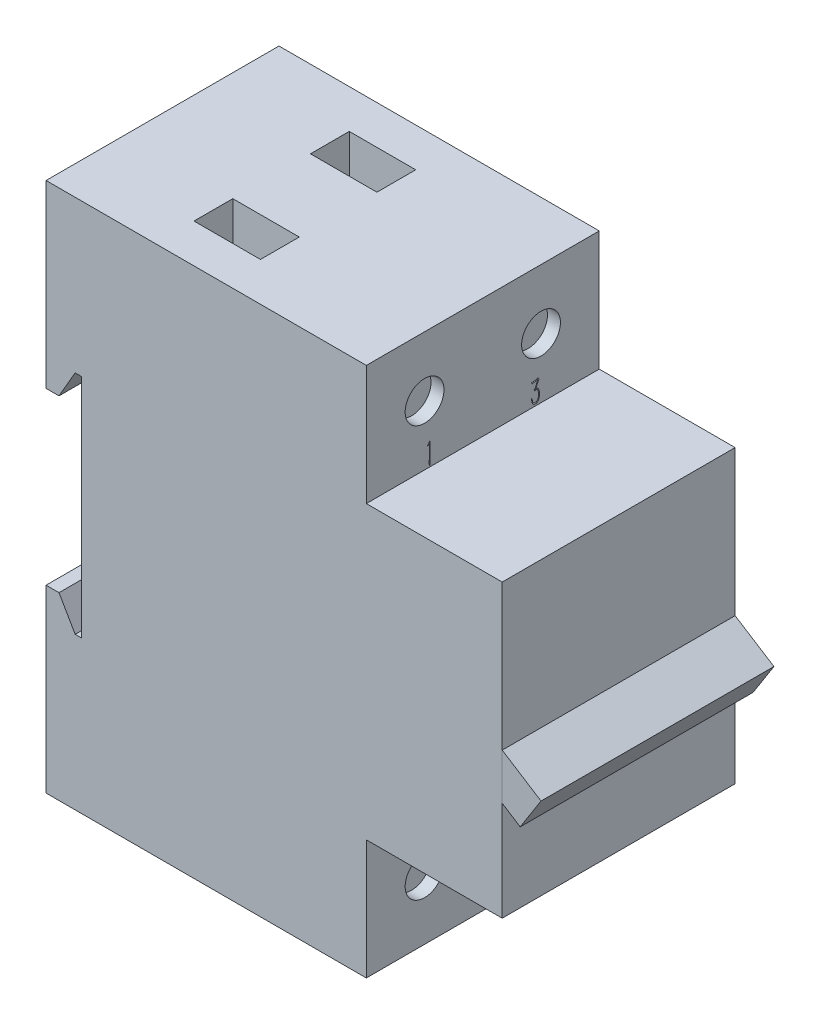
SolidWorks part; units mm, degrees
material "普通碳钢"
ref_plane "前视基准面" through (0, 0, 0) normal (0, 0, 1) x (1, 0, 0)
ref_plane "上视基准面" through (0, 0, 0) normal (0, 1, 0) x (1, 0, 0)
ref_plane "右视基准面" through (0, 0, 0) normal (1, 0, 0) x (0, 0, -1)
sketch "草图1" plane through (0, 0, 0) normal (0, 0, 1) x (1, 0, 0)
  line L0 (0, 0) -> (97.4474, 0) construction
  line L1 (0, 13.1699) -> (2, 13.1699)
  line L2 (2, 13.1699) -> (4.5, 17.5)
  line L3 (4.5, 17.5) -> (5.5, 17.5)
  line L4 (5.5, 17.5) -> (5.5, -17.5)
  line L5 (0, 13.1699) -> (0, 41)
  line L6 (0, 41) -> (49.5, 41)
  line L7 (49.5, 41) -> (49.5, 22.5)
  line L8 (49.5, 22.5) -> (70.5, 22.5)
  line L9 (70.5, 22.5) -> (70.5, -22.5)
  line L10 (49.5, -22.5) -> (70.5, -22.5)
  line L11 (49.5, -41) -> (49.5, -22.5)
  line L12 (0, -41) -> (49.5, -41)
  line L13 (0, -13.1699) -> (0, -41)
  line L14 (4.5, -17.5) -> (5.5, -17.5)
  line L15 (2, -13.1699) -> (4.5, -17.5)
  line L16 (0, -13.1699) -> (2, -13.1699)
  point P14 (70.5, 0)
  point P19 (5.5, 0)
  dimension "D1" = 35
  dimension "D2" = 45
  dimension "D3" = 82
  dimension "D4" = 5.5
  dimension "D5" = 1
  dimension "D6" = 2
  dimension "D7" = 120
  dimension "D8" = 44
  dimension "D9" = 65
extrude "凸台-拉伸1" add sketch "草图1" against normal blind 18
sketch "草图2" plane through (49.5, 0, 0) normal (1, 0, 0) x (0, 0, -1)
  line L0 (0, 22.5) -> (0, 41) construction
  line L1 (18, 41) -> (0, 41) construction
  circle A0 centre (9, 31.75) radius 3
  point P4 (0, 31.75)
  point P7 (9, 41)
  dimension "D1" = 6
extrude "切除-拉伸1" cut sketch "草图2" against normal blind 2
sketch "草图7" plane through (0, 41, 0) normal (0, 1, 0) x (1, 0, 0)
  line L0 (0, 18) -> (0, 0) construction
  line L1 (16.8628, 6) -> (27.1372, 6)
  line L2 (16.8628, 6) -> (16.8628, 12)
  line L3 (16.8628, 12) -> (27.1372, 12)
  line L4 (27.1372, 6) -> (27.1372, 12)
  line L5 (16.8628, 6) -> (27.1372, 12) construction
  line L6 (16.8628, 12) -> (27.1372, 6) construction
  point P0 (22, 9)
  point P7 (0, 9)
  dimension "D1" = 22
  dimension "D2" = 6
extrude "切除-拉伸2" cut sketch "草图7" against normal blind 8
mirror "镜向1" about plane through (0, 0, 0) normal (0, 1, 0) of "切除-拉伸2", "切除-拉伸1"
sketch "草图3" plane through (47.5, 0, 0) normal (1, 0, 0) x (0, 0, -1)
  point P0 (9, 31.75)
  point P1 (9, -31.75)
sketch "草图4" plane through (0, 0, 0) normal (0, 0, 1) x (1, 0, 0)
  line L0 (70.5, 0) -> (76.5, -3.812)
  line L1 (70.5, -22.5) -> (70.5, 22.5) construction
  line L2 (76.5, -3.812) -> (73.2825, -8.8763)
  line L3 (73.2825, -8.8763) -> (70.5, -7.1085)
  line L4 (70.5, -7.1085) -> (70.5, 0)
  line L5 (5.5, 17.5) -> (5.5, -17.5) construction
  dimension "D1" = 71
  dimension "D2" = 6
  dimension "D3" = 57.571
extrude "凸台-拉伸3" add sketch "草图4" against normal through all
sketch "草图5" plane through (0, 0, 0) normal (0, 0, 1) x (1, 0, 0)
  line L0 (70.5, 0) -> (70.5, -7.1085)
split line "分割线1"
chamfer "倒角1" [suppressed] distance 0.2 angle 45
pattern_linear "阵列(线性)1" count 2 spacing 18 along (0, 0, -1) of bodies 106 109
combine bodies "组合1" operation type add bodies to combine 110 106
sketch "草图11" [suppressed] plane through (45.5, 0, 0) normal (1, 0, 0) x (0, 0, -1)
  line L0 (8.499, 23.3046) -> (27.7665, 23.3046) construction
sketch "草图10" plane through (49.5, 0, 0) normal (1, 0, 0) x (0, 0, -1)
  line L0 (7.5191, -26.5) -> (26.9428, -26.5) construction
  line L1 (36, -22.5) -> (0, -22.5) construction
  text T0 "1        3"
  text T1 "24"
  dimension "D1" = 4
extrude "切除-拉伸3" cut sketch "草图10" against normal blind 1
sketch "草图8" plane through (0, 33, 0) normal (0, 1, 0) x (1, 0, 0)
  point P0 (22, 9)
  point P1 (20, 27.0065)
sketch "草图9" plane through (0, -33, 0) normal (0, -1, 0) x (1, 0, 0)
  point P0 (22, -9)
  point P1 (20.8339, -27.351)
sketch "0_0_Point" plane through (0, 33, 0) normal (0, 1, 0) x (1, 0, 0)
  point P0 (22, 9)
other "0_0" parameters "直径"=2, "端头长度"=2
ref_axis "基准轴1" through (22, 43, -9) along (0, -1, 0)
sketch "0_1_Point" plane through (0, -33, 0) normal (0, -1, 0) x (1, 0, 0)
  point P0 (22, -9)
other "0_1" parameters "直径"=2, "端头长度"=2
ref_axis "基准轴2" through (22, -43, -9) along (0, 1, 0)
sketch "1_0_Point" plane through (0, 33, 0) normal (0, 1, 0) x (1, 0, 0)
  point P0 (20, 27.0065)
other "1_0" parameters "直径"=2, "端头长度"=2
ref_axis "基准轴3" through (20, 43, -27.0065) along (0, -1, 0)
sketch "1_1_Point" plane through (0, -33, 0) normal (0, -1, 0) x (1, 0, 0)
  point P0 (20.8339, -27.351)
other "1_1" parameters "直径"=2, "端头长度"=2
ref_axis "基准轴4" through (20.8339, -43, -27.351) along (0, 1, 0)
equation "\"D1@草图7\"=\"D8@草图1\"/2"
